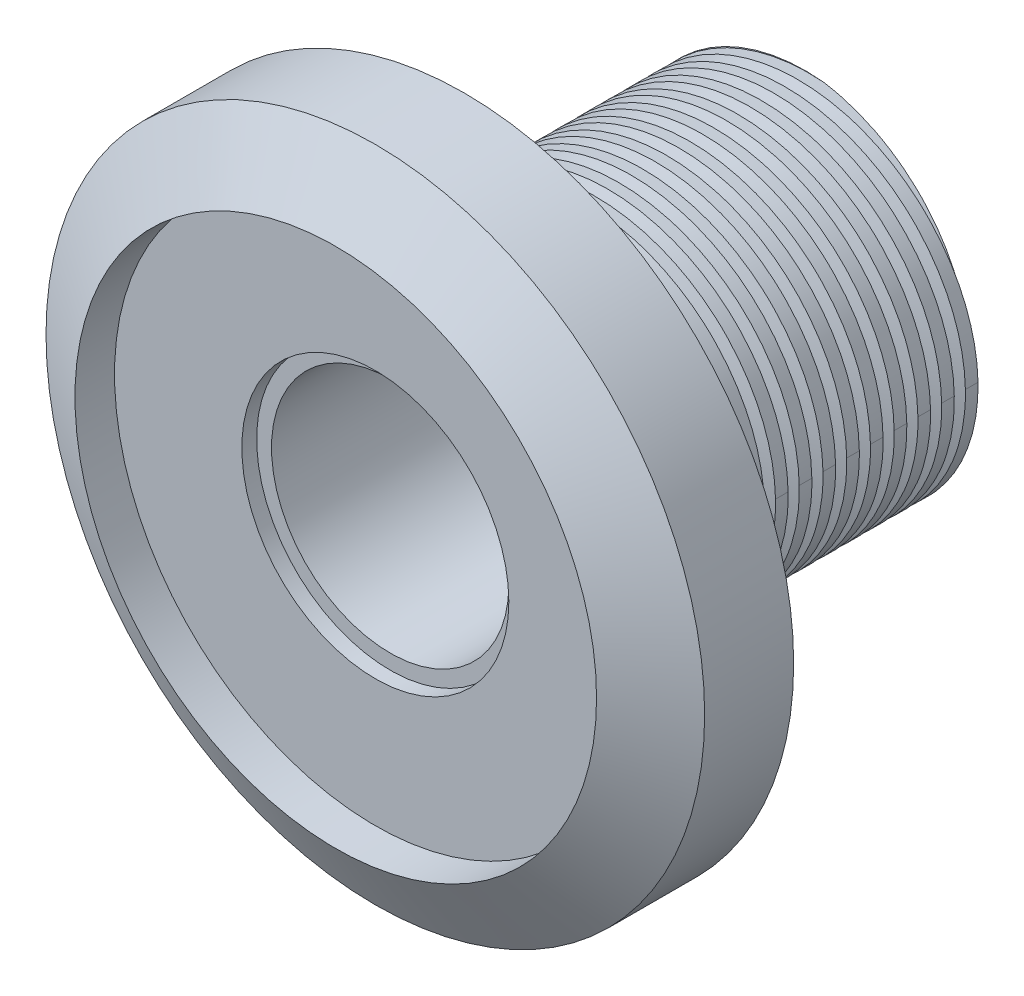
SolidWorks part; units mm, degrees
ref_plane "Front Plane" through (0, 0, 0) normal (0, 0, 1) x (1, 0, 0)
ref_plane "Top Plane" through (0, 0, 0) normal (0, 1, 0) x (1, 0, 0)
ref_plane "Right Plane" through (0, 0, 0) normal (1, 0, 0) x (0, 0, -1)
sketch "Sketch1" plane through (0, 0, 0) normal (0, 0, 1) x (1, 0, 0)
  circle A0 centre (0, 0) radius 6
  dimension "D1" = 12
extrude "Boss-Extrude1" add sketch "Sketch1" along normal blind 11.5
sketch "Sketch2" plane through (0, 0, 11.5) normal (0, 0, 1) x (1, 0, 0)
  circle A0 centre (0, 0) radius 11.1
  dimension "D1" = 22.2
extrude "Boss-Extrude2" add sketch "Sketch2" along normal blind 3
sketch "Sketch3" plane through (0, 0, 14.5) normal (0, 0, 1) x (1, 0, 0)
  circle A0 centre (0, 0) radius 4.5
  dimension "D1" = 9
extrude "Cut-Extrude1" cut sketch "Sketch3" against normal blind 0.5
sketch "Sketch4" plane through (0, 0, 0) normal (0, 1, 0) x (1, 0, 0)
  line L0 (5.5, 0) -> (6.5, 0.375)
  line L1 (6, 0) -> (-6, 0) construction
  line L2 (6.5, 0.375) -> (6.5, -0.375)
  line L3 (6.5, -0.375) -> (5.5, 0)
  dimension "D1" = 1
  dimension "D2" = 0.75
  dimension "D3" = 0.375
  dimension "D4" = 5.5
sketch "Sketch5" plane through (0, 0, 0) normal (0, 0, -1) x (-1, 0, 0)
  circle A0 centre (0, 0) radius 6
curve "Helix/Spiral1" pitch 0.8 height 8.8 radius 6 centre (0, 0, 0) axis (0, 0, 1) start towards (1, 0, 0)
sweep "Cut-Sweep1" cut profiles "Sketch4" path "Helix/Spiral1" align with end faces yes
sketch "Sketch6" plane through (0, 0, 14) normal (0, 0, 1) x (1, 0, 0)
  circle A0 centre (0, 0) radius 4
  dimension "D1" = 8
extrude "Cut-Extrude2" cut sketch "Sketch6" against normal blind 17
sketch "Sketch7" plane through (0, 0, 0) normal (0, 1, 0) x (1, 0, 0)
  line L0 (-11.1, -14.5) -> (0, -20.9086) construction
  line L1 (0, -20.9086) -> (11.1, -14.5) construction
  line L2 (-11.1, -14.5) -> (-8.79, -14.5)
  line L3 (-11.1, -14.5) -> (11.1, -14.5) construction
  line L4 (-8.79, -14.5) -> (-8.79, -15.8337)
  line L5 (-8.79, -15.8337) -> (-11.1, -14.5)
  line L6 (0, -20.9086) -> (0, 0) construction
  dimension "D1" = 120
  dimension "D2" = 8.79
revolve "Revolve1" add sketch "Sketch7" angle 360 about L6
